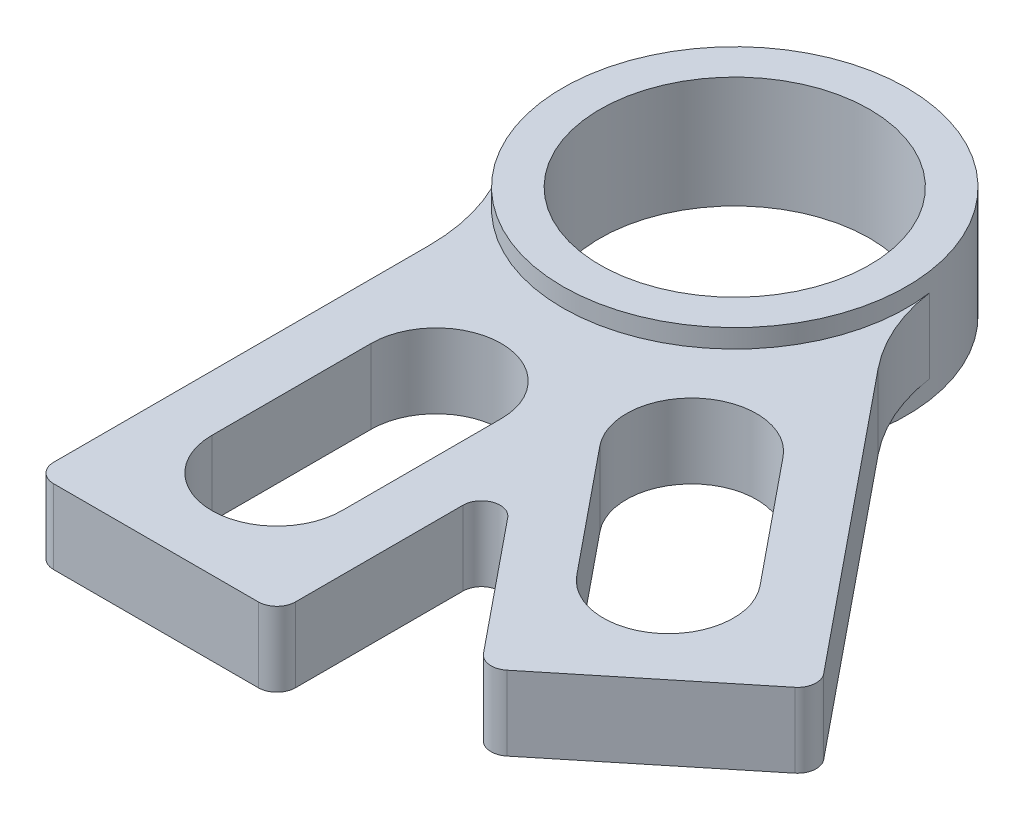
SolidWorks part; units mm, degrees
material "AISI 4130 Steel, annealed at 865C"
ref_plane "Front Plane" through (0, 0, 0) normal (0, 0, 1) x (1, 0, 0)
ref_plane "Top Plane" through (0, 0, 0) normal (0, 1, 0) x (1, 0, 0)
ref_plane "Right Plane" through (0, 0, 0) normal (1, 0, 0) x (0, 0, -1)
sketch "Sketch1" plane through (0, 0, 0) normal (0, 1, 0) x (1, 0, 0)
  line L0 (0, 0) -> (0, -49.3903) construction
  line L1 (0, 0) -> (31.1614, -38.3193) construction
  line L2 (0, -39.0716) -> (0, -25.4826) construction
  line L3 (-5.5562, -39.0716) -> (-5.5562, -25.4826)
  line L4 (5.5563, -39.0716) -> (5.5563, -25.4826)
  line L5 (24.651, -30.3136) -> (16.0775, -19.7706) construction
  line L6 (20.3402, -33.8191) -> (11.7667, -23.2761)
  line L7 (28.9618, -26.808) -> (20.3883, -16.265)
  line L8 (0, -49.3903) -> (0, -44.6278) construction
  line L9 (31.1614, -38.3193) -> (28.1566, -34.6244) construction
  line L10 (-10.3187, -49.3903) -> (10.3188, -49.3903)
  line L11 (23.1556, -44.8296) -> (39.1671, -31.809)
  line L12 (-10.3187, -49.3903) -> (-10.3187, -10.4432)
  line L13 (10.3188, -49.3903) -> (10.3188, -29.0441)
  line L14 (39.1671, -31.809) -> (14.5946, -1.592)
  line L15 (23.1556, -44.8296) -> (10.3188, -29.0441)
  line L16 (182.1331, -223.9704) -> (14.0958, -17.3337) construction
  line L22 (0, 0) -> (10.3188, -29.0441) construction
  circle A0 centre (0, 0) radius 11.5062
  circle A1 centre (0, 0) radius 14.6812
  arc A2 (-5.5562, -39.0716) -> (5.5563, -39.0716) centre (0, -39.0716) ccw
  arc A3 (5.5563, -25.4826) -> (-5.5562, -25.4826) centre (0, -25.4826) ccw
  arc A4 (20.3402, -33.8191) -> (28.9618, -26.808) centre (24.651, -30.3136) ccw
  arc A5 (20.3883, -16.265) -> (11.7667, -23.2761) centre (16.0775, -19.7706) ccw
  point P8 (0, -32.2771)
  point P13 (20.3643, -25.0421)
  point P25 (0, -49.3903)
  point P27 (31.1614, -38.3193)
  dimension "D2" = 29.3624
  dimension "D3" = 4.7625
  dimension "D4" = 4.7625
  dimension "D5" = 13.589
  dimension "D6" = 49.3903
  dimension "D7" = 20.6375
extrude "Bearing_Insert_Extrude" add sketch "Sketch1" along normal mid plane 9.525 contours A1 A0 region at (-5.4988, 0, -13.1636)
extrude "Apex_Slot_Insert_Extrude" add sketch "Sketch1<4>" along normal mid plane 6.35 contours A1 L12 L10 L13 L15 L11 L14 A5 L7 A4 L6 A3 L4 A2 L3 region at (10.0871, 0, 28.3921)
sketch "Sketch1<4>" plane through (0, 0, 0) normal (0, 1, 0) x (1, 0, 0) same geometry as "Sketch1"
fillet "Fillet1" radius 16.002 2 edges at (14.5946, 0, 1.592) (-10.3187, 0, 10.4432)
fillet "Fillet2" radius 1.5875 5 edges at (39.1671, 0, 31.809) (23.1556, 0, 44.8296) (10.3188, 0, 29.0441) (10.3188, 0, 49.3903) (-10.3187, 0, 49.3903)
equation "\"Apex_thickness\"= .25"
equation "\"Bearing_diameter\"= 0.906in"
equation "\"A-arm_angle\"= 39.1893"
equation "\"D1@Sketch1\"=\"Bearing_diameter\""
equation "\"D1@Apex_Slot_Insert_Extrude\"=\"Apex_thickness\""
